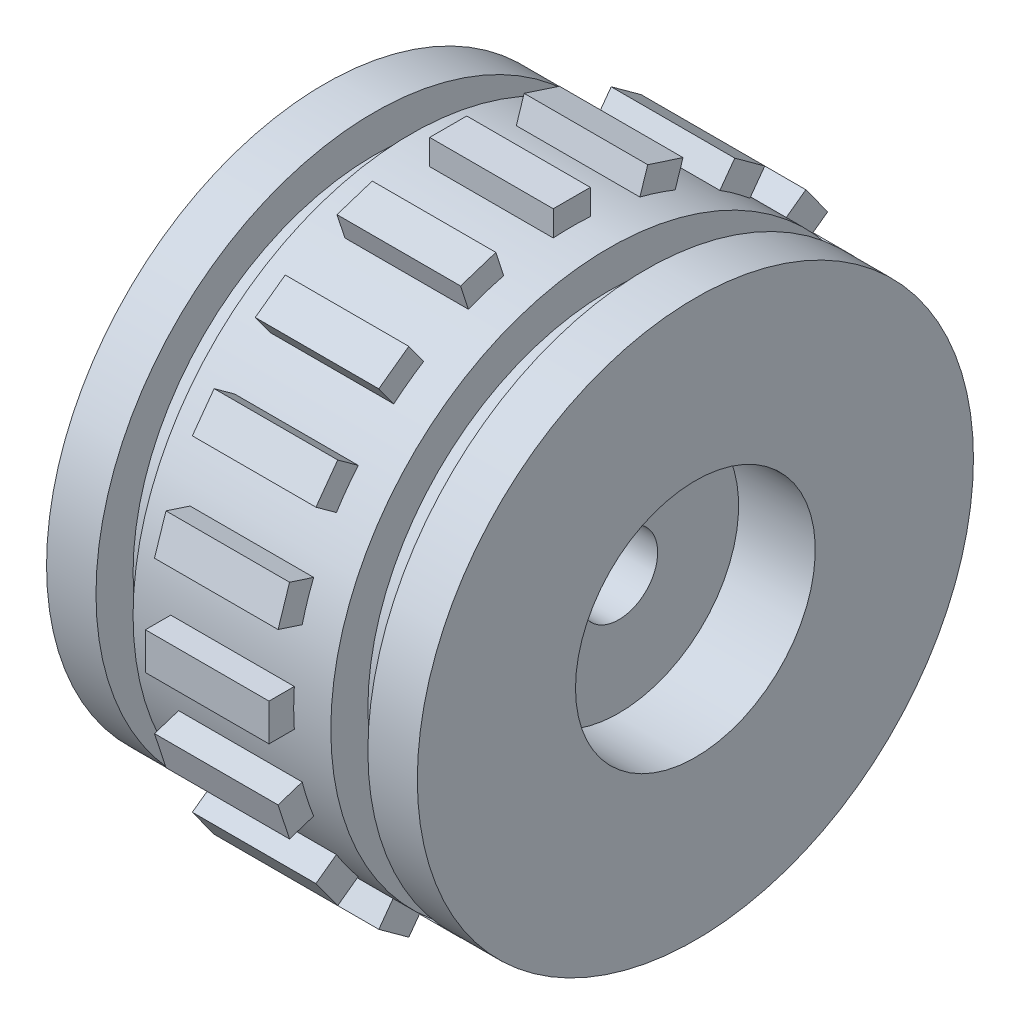
SolidWorks part; units mm, degrees
material "ABS"
ref_plane "Спереди" through (0, 0, 0) normal (0, 0, 1) x (1, 0, 0)
ref_plane "Сверху" through (0, 0, 0) normal (0, 1, 0) x (1, 0, 0)
ref_plane "Справа" through (0, 0, 0) normal (1, 0, 0) x (0, 0, -1)
sketch "Эскиз4" plane through (0, 0, 0) normal (0, 0, 1) x (1, 0, 0)
  line L0 (-30, 0) -> (0, 0) construction
  line L1 (-30, 22.5) -> (-30, 18.5)
  line L2 (-30, 18.5) -> (-19, 18.5)
  line L4 (-19, 18.5) -> (-19, 5.1)
  line L5 (-13, 3.15) -> (0, 3.15)
  line L9 (0, 22.5) -> (-30, 22.5)
  line L11 (-6.2, 3.15) -> (-6.2, 9.7)
  line L15 (0, 22.5) -> (0, 3.15)
  line L17 (-19, 5.1) -> (-13, 5.1)
  line L18 (-13, 5.1) -> (-13, 3.15)
  line L19 (-6.2, 9.7) -> (0, 9.7)
  dimension "D2" = 6
  dimension "D3" = 6.3
  dimension "D4" = 6.2
  dimension "D5" = 45
  dimension "D6" = 10.2
  dimension "D7" = 19.4
  dimension "D8" = 4
  dimension "D9" = 30
  dimension "D12" = 11
revolve "Повернуть1" add sketch "Эскиз4" angle 360 about L0 region at (-11.8483, 14.7713, 0)
chamfer "Фаска2" distance 2 angle 45 2 edges at (-30, 0, 18.5) (-19, 0, 18.5)
sketch "Эскиз6" plane through (0, 0, 0) normal (0, 0, 1) x (1, 0, 0)
  line L0 (-30, 18.5) -> (-30, 23.5)
  line L1 (-30, 22.5) -> (-30, -22.5) construction
  line L2 (-30, 23.5) -> (-26, 23.5)
  line L3 (-26, 23.5) -> (-26, 19.5)
  line L4 (-26, 19.5) -> (-23, 19.5)
  line L5 (-23, 19.5) -> (-23, 23.5)
  line L6 (-23, 23.5) -> (-7, 23.5)
  line L7 (-7, 23.5) -> (-7, 19.5)
  line L8 (-7, 19.5) -> (-4, 19.5)
  line L9 (-4, 19.5) -> (-4, 23.5)
  line L10 (-4, 23.5) -> (0, 23.5)
  line L11 (0, 23.5) -> (0, 18.5)
  line L12 (0, -22.5) -> (0, 22.5) construction
  line L13 (0, 18.5) -> (-30, 18.5)
  line L14 (0, 22.5) -> (-30, 22.5) construction
  line L15 (-15, 25.3568) -> (-15, 13.0667) construction
  line L16 (-26, 23.5) -> (-23, 23.5)
  line L17 (-7, 23.5) -> (-4, 23.5)
  dimension "D1" = 4
  dimension "D2" = 5
  dimension "D3" = 1
  dimension "D4" = 4
  dimension "D5" = 3
revolve "Вырез-Повернуть2" cut sketch "Эскиз6" angle 360 about L0 region at (-24.5, 21.5, 0) region at (-5.5, 21.5, 0)
sketch "Эскиз7" plane through (0, 0, 0) normal (0, 0, 1) x (1, 0, 0)
  line L0 (-15, 26.6765) -> (-15, 11.8247) construction
  line L1 (-20, 24.5) -> (-10, 24.5)
  line L2 (-20, 24.5) -> (-20, 21.0633)
  line L3 (-20, 21.0633) -> (-10, 21.0633)
  line L4 (-10, 24.5) -> (-10, 21.0633)
  line L5 (-30, 22.5) -> (-30, -22.5) construction
  line L6 (0, -22.5) -> (0, 22.5) construction
  line L7 (-7, 22.5) -> (-23, 22.5) construction
  dimension "D1" = 10
  dimension "D2" = 2
extrude "Бобышка-Вытянуть1" add sketch "Эскиз7" along normal mid plane 3
pattern_circular "Круговой массив1" count 20 over 360 about axis through (-30, 0, 0) along (-1, 0, 0) of "Бобышка-Вытянуть1"
